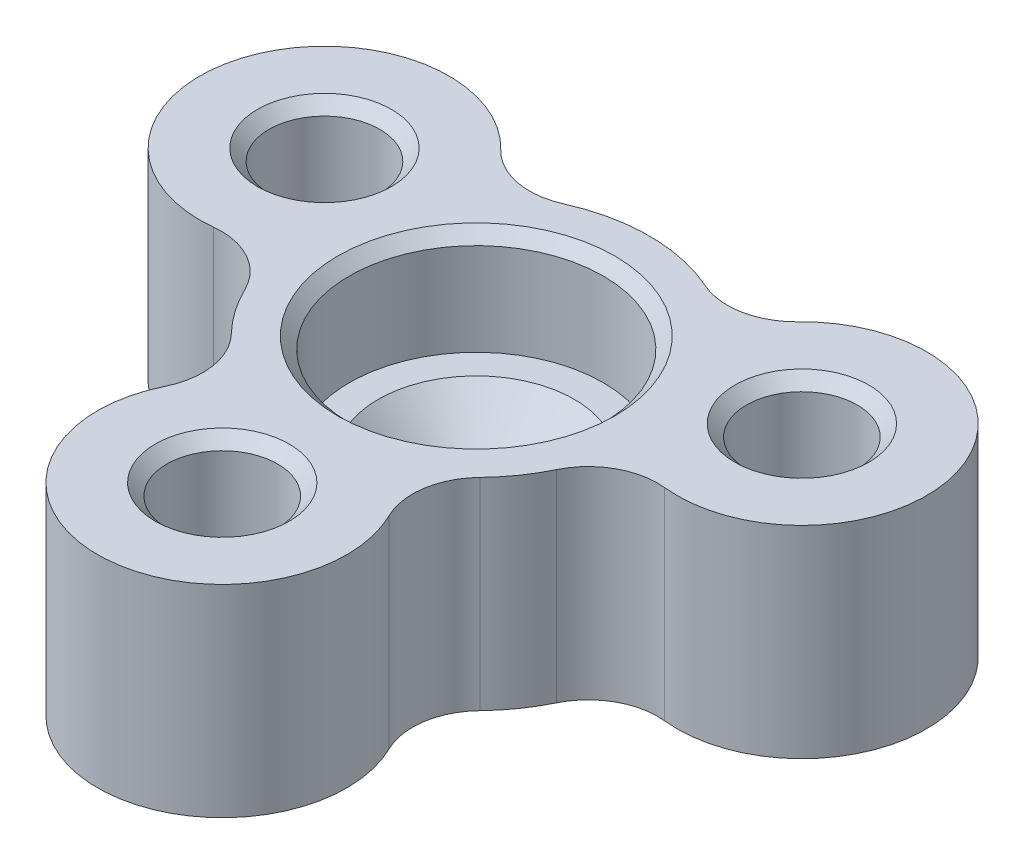
SolidWorks part; units mm, degrees
ref_plane "Plan de face" through (0, 0, 0) normal (0, 0, 1) x (1, 0, 0)
ref_plane "Plan de dessus" through (0, 0, 0) normal (0, 1, 0) x (1, 0, 0)
ref_plane "Plan de droite" through (0, 0, 0) normal (1, 0, 0) x (0, 0, -1)
sketch "Sketch1" plane through (0, 0, 0) normal (0, 1, 0) x (1, 0, 0)
  line L0 (0, 0) -> (0, -11) construction
  line L1 (0, 0) -> (-10.3366, 3.7622) construction
  line L2 (0, 0) -> (10.3366, 3.7622) construction
  circle A5 centre (0, 0) radius 5.5 construction
  circle A12 centre (0, -11) radius 2.4 construction
  arc A13 (-3.3074, -6.7314) -> (3.3074, -6.7314) centre (0, -11) ccw
  arc A14 (-7.4566, -0.8057) -> (-3.3074, -6.7314) centre (0, 0) ccw
  arc A19 (5.1942, 5.4102) -> (-5.1942, 5.4102) centre (0, 0) ccw
  arc A20 (3.3074, -6.7314) -> (7.4566, -0.8057) centre (0, 0) ccw
  circle A23 centre (0, -11) radius 1.7
  circle A24 centre (-10.3366, 3.7622) radius 1.7
  circle A25 centre (-10.3366, 3.7622) radius 2.4 construction
  arc A26 (-5.1942, 5.4102) -> (-7.4566, -0.8057) centre (-10.3366, 3.7622) ccw
  circle A27 centre (10.3366, 3.7622) radius 1.7
  circle A28 centre (10.3366, 3.7622) radius 2.4 construction
  arc A29 (7.4566, -0.8057) -> (5.1942, 5.4102) centre (10.3366, 3.7622) ccw
  dimension "D1" = 2
  dimension "D4" = 3
  dimension "D2" = 11
  dimension "D3" = 4.8
  dimension "D6" = 110
  dimension "D7" = 3.4
  dimension "D5" = 11
  dimension "D8" = 110
extrude "Boss-Extrude1" add sketch "Sketch1" against normal blind 8.7483 contours A5 | A5 | A25 A24 | A12 A23 | A13 A20 A19 A14 A12 A25 region at (0, 0, 0.6749)
hole_wizard "Ø4.8 (4.8) Diameter Hole1" positions "Esquisse3" profile "Esquisse2" hole size "Ø4.8" standard "ANSI Metric"
sketch "Esquisse3" plane through (0, 0, 0) normal (0, 1, 0) x (1, 0, 0)
  point P0 (-10.3366, 3.7622)
  point P3 (10.3366, 3.7622)
  point P6 (0, -11)
sketch "Esquisse2" plane through (-10.3366, 0, -3.7622) normal (1, 0, 0) x (0, 0, 1)
  line L0 (0, 0) -> (0, 7.8421)
  line L1 (0, 7.8421) -> (2.4, 6.4)
  line L2 (2.4, 6.4) -> (2.4, 0)
  line L5 (2.4, 0) -> (0, 0)
  line L10 (0, 7.8421) -> (-2.4, 6.4) construction
  line L11 (0, -6.35) -> (0, 107.95) construction
  dimension "Hole Dia." = 4.8
  dimension "Hole Depth" = 6.4
  dimension "Drill Angle" = 118
chamfer "Chanfrein3" distance 0.5 angle 45 3 edges at (0, 0, 13.4) (10.3366, 0, -1.3622) (-10.3366, 0, -1.3622)
sketch "Sketch2" plane through (0, 0, 0) normal (1, 0, 0) x (0, 0, -1)
  line L0 (0, 1.699) -> (0, -5.7208) construction
  line L1 (0, 0) -> (6, 0)
  line L3 (5.5, -0.5) -> (5.5, -4.5)
  line L4 (5.5, -4.5) -> (4.25, -4.5)
  line L5 (4.25, -4.5) -> (4.25, -6.5)
  line L6 (4.25, -6.5) -> (0, -6.5)
  line L7 (0, -6.5) -> (0, 0)
  line L8 (5.5, -0.5) -> (6, 0)
  dimension "D1" = 4.25
  dimension "D2" = 2
  dimension "D3" = 4
  dimension "D4" = 0.5
  dimension "D5" = 45
  dimension "D6" = 5.5
revolve "Cut-Revolve1" cut sketch "Sketch2" angle 360 about L0
fillet "Fillet1" radius 3 6 edges at (-3.3074, -4.3741, 6.7314) (3.3074, -4.3741, 6.7314) (-7.4566, -4.3741, 0.8057) (-5.1942, -4.3741, -5.4102) (5.1942, -4.3741, -5.4102) (7.4566, -4.3741, 0.8057)
chamfer "Chanfrein2" distance 2 angle 45 1 edges at (0, -6.5, 4.25)
